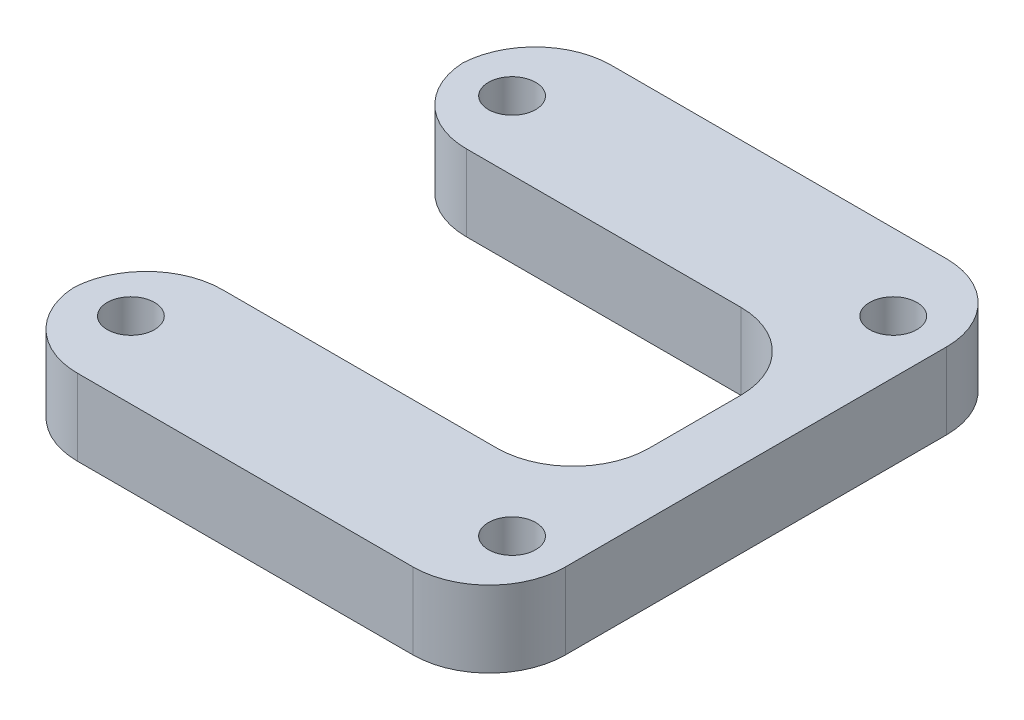
SolidWorks part; units mm, degrees
ref_plane "Alzado" through (0, 0, 0) normal (0, 0, 1) x (1, 0, 0)
ref_plane "Planta" through (0, 0, 0) normal (0, 1, 0) x (1, 0, 0)
ref_plane "Vista lateral" through (0, 0, 0) normal (1, 0, 0) x (0, 0, -1)
sketch "Croquis2" plane through (0, 0, 0) normal (0, 1, 0) x (1, 0, 0)
  line L5 (0, 27.4696) -> (0, -39.1615) construction
  line L6 (16, 17.5) -> (-16, 17.5)
  line L10 (16, 17.5) -> (16, -17.5)
  line L14 (16, -17.5) -> (-16, -17.5)
  line L38 (-16, 17.5) -> (-16, -17.5)
  line L39 (16, 17.5) -> (-16, -17.5) construction
  line L40 (16, -17.5) -> (-16, 17.5) construction
  line L41 (41.3864, 0) -> (-48.8219, 0) construction
  line L42 (-16, -8) -> (12, -8)
  line L43 (12, -8) -> (12, 8)
  line L44 (12, 8) -> (-16, 8)
  circle A8 centre (-12.5, -12.5) radius 1.55
  circle A9 centre (12.5, -12.5) radius 1.55
  circle A10 centre (12.5, 12.5) radius 1.55
  circle A11 centre (-12.5, 12.5) radius 1.55
  point P0 (0, 0)
  dimension "D12" = 25
  dimension "D10" = 3.1
  dimension "D13" = 12.5
  dimension "D1" = 35
  dimension "D2" = 32
  dimension "D3" = 2
  dimension "D4" = 2
  dimension "D5" = 12.5
  dimension "D6" = 12.5
  dimension "D7" = 9.5
  dimension "D8" = 9.5
  dimension "D9" = 28
  dimension "D11" = 25
extrude "Saliente-Extruir1" add sketch "Croquis2" along normal blind 5 contours L44 L43 L42 L38 L14 L10 L6 A11 A10 A9 A8 region at (15.5258, 0, 0)
fillet "Redondeo9" radius 5 8 edges at (-16, 2.5, 8) (-16, 2.5, 17.5) (-16, 2.5, -17.5) (16, 2.5, -17.5) (12, 2.5, 8) (12, 2.5, -8) (-16, 2.5, -8) (16, 2.5, 17.5)
